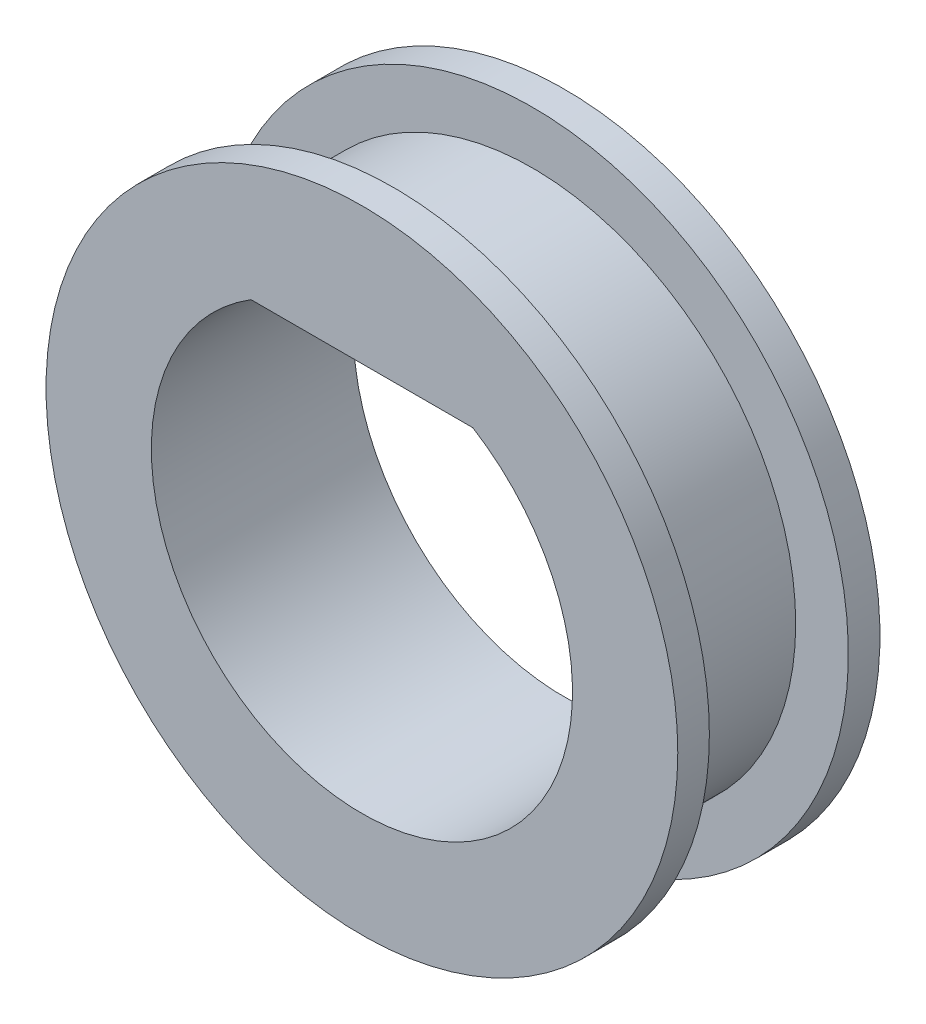
SolidWorks part; units mm, degrees
ref_plane "Front Plane" through (0, 0, 0) normal (0, 0, 1) x (1, 0, 0)
ref_plane "Top Plane" through (0, 0, 0) normal (0, 1, 0) x (1, 0, 0)
ref_plane "Right Plane" through (0, 0, 0) normal (1, 0, 0) x (0, 0, -1)
sketch "Sketch1" plane through (0, 0, 0) normal (0, 0, 1) x (1, 0, 0)
  circle A0 centre (0, 0) radius 12.5
  dimension "D1" = 25
extrude "Boss-Extrude1" add sketch "Sketch1" along normal mid plane 6.6
sketch "Sketch2" plane through (0, 0, -3.3) normal (0, 0, -1) x (-1, 0, 0)
  circle A0 centre (0, 0) radius 15
  dimension "D1" = 30
extrude "Boss-Extrude2" add sketch "Sketch2" along normal blind 1.5
sketch "Sketch3" plane through (0, 0, 3.3) normal (0, 0, 1) x (1, 0, 0)
  circle A0 centre (0, 0) radius 15
  dimension "D1" = 30
extrude "Boss-Extrude3" add sketch "Sketch3" along normal blind 1.5
sketch "Sketch4" plane through (0, 0, 4.8) normal (0, 0, 1) x (1, 0, 0)
  line L0 (-5.2678, 8.5) -> (5.2678, 8.5)
  circle A0 centre (0, 0) radius 10
  dimension "D1" = 20
  dimension "D2" = 8.5
extrude "Cut-Extrude1" cut sketch "Sketch4" against normal through all both and the other way through all contours L0 A0 region at (0, -0.3212, 4.8)
